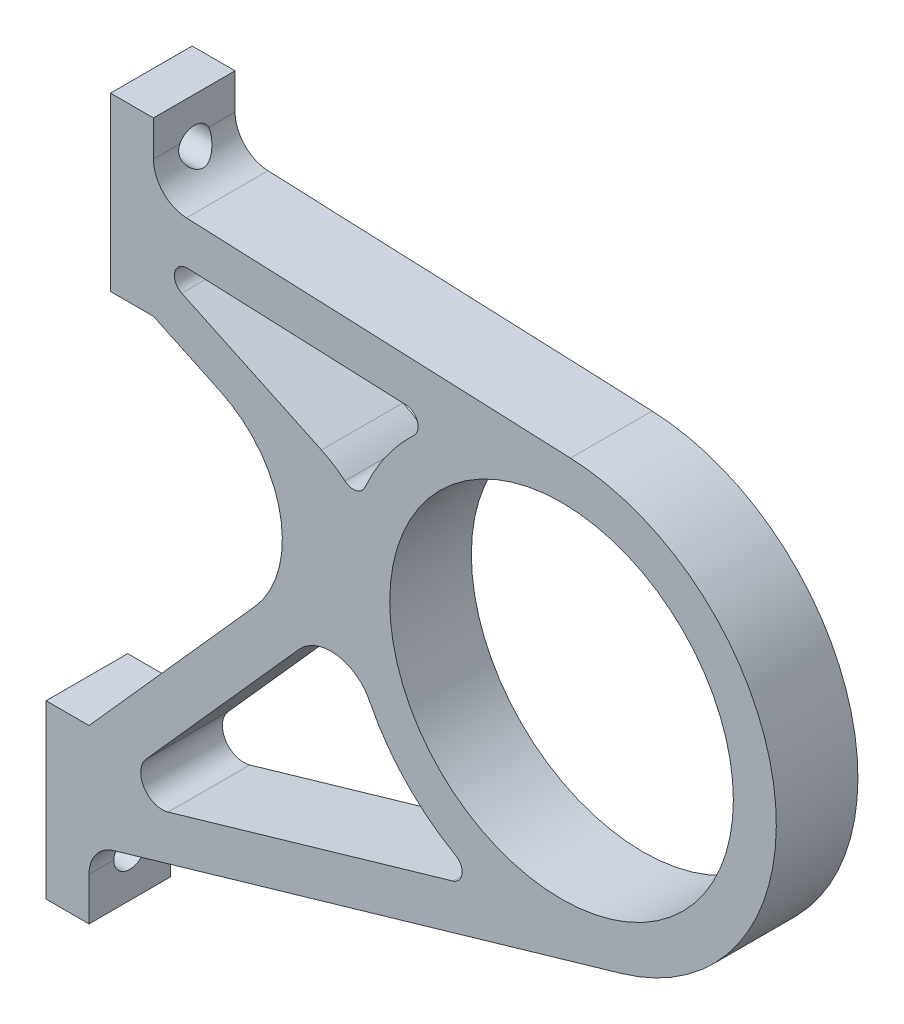
SolidWorks part; units mm, degrees
ref_plane "Front Plane" through (0, 0, 0) normal (0, 0, 1) x (1, 0, 0)
ref_plane "Top Plane" through (0, 0, 0) normal (0, 1, 0) x (1, 0, 0)
ref_plane "Right Plane" through (0, 0, 0) normal (1, 0, 0) x (0, 0, -1)
sketch "Sketch1" plane through (0, 0, 0) normal (0, 0, 1) x (1, 0, 0)
  line L0 (-133.35, 88.9) -> (-133.35, 38.1)
  line L1 (-133.35, 38.1) -> (-120.65, 38.1)
  line L2 (-133.35, 88.9) -> (-120.65, 88.9)
  line L3 (-120.65, 88.9) -> (-120.65, 68.58)
  line L4 (-120.65, 68.58) -> (2.6424, 63.445)
  line L5 (-152.4, -76.2) -> (-139.7, -76.2)
  line L6 (-152.4, -76.2) -> (-152.4, -127)
  line L7 (-152.4, -127) -> (-139.7, -127)
  line L8 (-139.7, -127) -> (-139.7, -106.68)
  line L9 (-139.7, -106.68) -> (17.7044, -60.982)
  line L10 (-120.65, 38.1) -> (-100.7551, 28.7158)
  line L11 (-139.7, -76.2) -> (-90.6011, -21.1288)
  line L12 (-46.0374, 52.7615) -> (-110.4951, 55.4461)
  line L13 (-112.2791, 48.1935) -> (-70.9856, 28.7158)
  line L14 (-77.621, -25.6539) -> (-122.808, -76.3375)
  line L15 (-116.2978, -86.6614) -> (-32.1185, -62.2223)
  arc A0 (-56.7845, -28.4212) -> (-31.3026, -55.2485) centre (0, 0) ccw
  circle A1 centre (0, 0) radius 50.8
  arc A2 (-90.6011, -21.1288) -> (-100.7551, 28.7158) centre (-114.3, 0) ccw
  arc A3 (-64.0429, 24.2554) -> (-70.9856, 28.7158) centre (-84.5305, 0) ccw
  arc A4 (-110.4951, 55.4461) -> (-112.2791, 48.1935) centre (-110.6537, 51.6394) ccw
  arc A6 (-122.808, -76.3375) -> (-116.2978, -86.6614) centre (-118.0683, -80.5632) ccw
  arc A7 (17.7044, -60.982) -> (2.6424, 63.445) centre (0, 0) ccw
  arc A8 (-43.5811, 46.1837) -> (-58.0985, 25.6283) centre (0, 0) ccw
  arc A9 (-46.0374, 52.7615) -> (-43.5811, 46.1837) centre (-46.196, 48.9548) cw
  arc A10 (-64.0429, 24.2554) -> (-58.0985, 25.6283) centre (-61.5844, 27.166) ccw
  arc A11 (-32.1185, -62.2223) -> (-31.3026, -55.2485) centre (-33.1808, -58.5634) ccw
  arc A12 (-77.621, -25.6539) -> (-56.7845, -28.4212) centre (-68.1415, -34.1055) cw
  point P26 (0, 0)
  point P30 (0, 0)
  point P31 (-73.377, -30.6798)
  point P33 (0, 0)
  point P36 (0, 0)
  point P37 (-70.0259, -17.135)
  point P38 (0, 0)
  point P39 (-63.1211, -6.9262)
  point P40 (-69.1069, -16.1041)
  point P41 (-69.1069, -16.1041)
  point P42 (-69.1069, -16.1041)
  point P43 (-87.1699, 0)
  point P44 (-35.9531, 52.3414)
  dimension "D1" = 12.7
  dimension "D2" = 101.6
  dimension "D13" = 63.5
  dimension "D14" = 31.75
  dimension "D17" = 3.81
  dimension "D18" = 31.75
  dimension "D21" = 6.35
  dimension "D22" = 3.81
  dimension "D23" = 3.81
  dimension "D24" = 12.7
  dimension "D3" = 50.8
  dimension "D4" = 12.7
  dimension "D5" = 20.32
  dimension "D6" = 133.35
  dimension "D7" = 152.4
  dimension "D8" = 12.7
  dimension "D9" = 50.8
  dimension "D10" = 20.32
  dimension "D11" = 88.9
  dimension "D12" = 127
  dimension "D15" = 12.7
  dimension "D16" = 12.7
  dimension "D19" = 12.7
  dimension "D20" = 12.7
extrude "Boss-Extrude1" add sketch "Sketch1" along normal blind 24.13
fillet "Fillet1" radius 10.16 2 edges at (-139.7, -106.68, 12.065) (-120.65, 68.58, 12.065)
sketch "Sketch2" plane through (-152.4, 0, 0) normal (-1, 0, 0) x (0, 0, 1)
  line L0 (24.13, 88.9) -> (0, 88.9) construction
  line L1 (24.13, -127) -> (0, -127) construction
  circle A0 centre (12.065, -114.3) radius 4.7625
  circle A1 centre (12.065, 76.2) radius 4.7625
  point P6 (12.065, 88.9)
  dimension "D1" = 9.525
  dimension "D2" = 12.7
  dimension "D3" = 12.7
extrude "Cut-Extrude1" cut sketch "Sketch2" against normal through all
